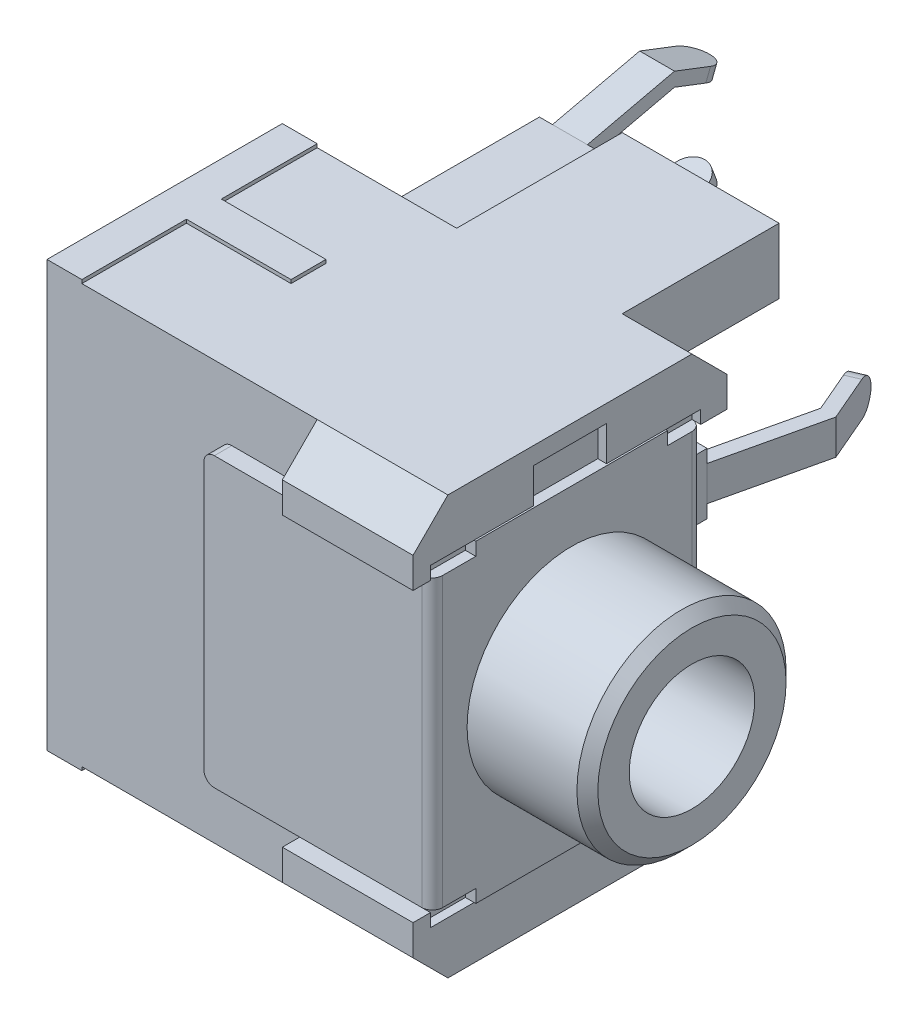
SolidWorks part; units mm, degrees
ref_plane "Front" through (0, 0, 0) normal (0, 0, 1) x (1, 0, 0)
ref_plane "Top" through (0, 0, 0) normal (0, 1, 0) x (1, 0, 0)
ref_plane "Right" through (0, 0, 0) normal (1, 0, 0) x (0, 0, -1)
sketch "Sketch1" plane through (0, 0, 0) normal (1, 0, 0) x (0, 0, -1)
  line L1 (-4.5, 6) -> (4.5, 6)
  line L2 (-4.5, 6) -> (-4.5, -6)
  line L3 (-4.5, -6) -> (4.5, -6)
  line L4 (4.5, 6) -> (4.5, -6)
  circle A0 centre (0, 0) radius 1.8
  dimension "ID" = 3.6
  dimension "H1" = 4.5
  dimension "Width" = 12
  dimension "Height" = 9
  dimension "H2" = 4.5
  dimension "W1" = 6
  dimension "W2" = 6
sketch "Sketch2" plane through (0, 0, 0) normal (0, 1, 0) x (1, 0, 0)
  line L0 (-3.5, 4.5) -> (-3.5, -4.5)
  line L1 (-3.5, 0) -> (0, 0) construction
  line L2 (-3.5, 3) -> (-3, 3) construction
  line L3 (-3.5, 3) -> (-3.5, -3) construction
  line L5 (-3.5, -3) -> (-3, -3) construction
  line L6 (-3, 3) -> (-3, -3) construction
  line L7 (-3, 3) -> (0, 3) construction
  line L8 (-3, 3) -> (-3, -3) construction
  line L9 (-3, -3) -> (0, -3) construction
  line L10 (-3.5, -4.5) -> (-15, -4.5)
  line L12 (-3.5, 4.5) -> (-15, 4.5)
  line L13 (-15, -4.5) -> (-15, 4.5)
  line L14 (0, 3) -> (0, -3) construction
  dimension "Length" = 11.5
  dimension "L2" = 3.5
  dimension "OD" = 6
  dimension "D_DIA" = 6
sketch "Sketch4" plane through (0, 0, 0) normal (0, 1, 0) x (1, 0, 0)
  line L1 (-3.5, 4.5) -> (-3.5, -4.5)
  line L4 (-15, -4.5) -> (-15, 4.5) construction
  line L5 (-3.5, -4.5) -> (-15, -4.5) construction
  line L15 (-3.5, 4.5) -> (-15, 4.5) construction
  line L20 (-15, -4.5) -> (-15, 4.5)
  line L21 (-3.5, -4.5) -> (-15, -4.5)
  line L31 (-3.5, 4.5) -> (-15, 4.5)
extrude "Extrude1" add sketch "Sketch4" along normal blind 6 and the other way blind 6
ref_plane "Plane1" through (-3, 0, 0) normal (1, 0, 0) x (0, 0, -1)
sketch "Sketch5" plane through (-3.5, 0, 0) normal (1, 0, 0) x (0, 0, -1)
  circle A0 centre (0, 0) radius 3
  dimension "OD" = 6
extrude "Extrude2" add sketch "Sketch5" along normal up to surface (0.5 mm away) up to plane "Plane1"
ref_plane "Plane2" through (-3, 0, 0) normal (1, 0, 0) x (0, 0, -1)
sketch "Sketch6" plane through (-3, 0, 0) normal (1, 0, 0) x (0, 0, -1)
  circle A0 centre (0, 0) radius 3
  dimension "D_DIA" = 6
extrude "Extrude3" add sketch "Sketch6" along normal up to surface (3 mm away) up to plane "Right"
sketch "Sketch12" plane through (0, 0, 0) normal (1, 0, 0) x (0, 0, -1)
  circle A0 centre (0, 0) radius 1.8 construction
  circle A3 centre (0, 0) radius 1.8
extrude "Cut-Extrude1" cut sketch "Sketch12" against normal up to surface (3.5 mm away) up to face at (-3.5, 0, 0)
chamfer "Chamfer1" distance 0.3 angle 45 1 edges at (0, 0, -3)
sketch "Sketch54" plane through (0, 0, 4.5) normal (0, 0, 1) x (1, 0, 0)
  line L0 (-15, -6) -> (-3.5, -6) construction
  line L1 (-15, 6) -> (-7.25, 6)
  line L2 (-15, 6) -> (-15, -6)
  line L3 (-15, -6) -> (-7.25, -6)
  line L4 (-7.25, 6) -> (-7.25, 4.125)
  line L5 (-3.5, 6) -> (-3.5, -6) construction
  line L6 (-7.25, 4.125) -> (-3.5, 4.125)
  line L8 (-7.25, -4.125) -> (-3.5, -4.125)
  line L9 (-3.5, 4.125) -> (-3.5, -4.125)
  line L10 (-7.25, -4.125) -> (-7.25, -6)
  point P12 (-3.5, 0)
  dimension "D1" = 8.25
  dimension "D3" = 3.75
extrude "Cut-Extrude17" cut sketch "Sketch54" against normal blind 1
sketch "Sketch56" plane through (0, 0, -4.5) normal (0, 0, -1) x (-1, 0, 0)
  line L8 (15, 6) -> (7.25, 6)
  line L9 (7.25, 6) -> (7.25, 4.125)
  line L10 (7.25, 4.125) -> (3.5, 4.125)
  line L11 (3.5, 4.125) -> (3.5, -4.125)
  line L12 (3.5, -4.125) -> (7.25, -4.125)
  line L13 (7.25, -4.125) -> (7.25, -6)
  line L14 (7.25, -6) -> (15, -6)
  line L15 (15, -6) -> (15, 6)
  line L16 (15, 6) -> (7.25, 6)
  line L17 (7.25, 6) -> (7.25, 4.125)
  line L18 (7.25, 4.125) -> (3.5, 4.125)
  line L19 (3.5, 4.125) -> (3.5, -4.125)
  line L20 (3.5, -4.125) -> (7.25, -4.125)
  line L21 (7.25, -4.125) -> (7.25, -6)
  line L22 (7.25, -6) -> (15, -6)
  line L23 (15, -6) -> (15, 6)
  dimension "D1" = 0
extrude "Cut-Extrude18" cut sketch "Sketch56" against normal blind 1.25
sketch "Sketch89" plane through (0, 0, -3.25) normal (0, 0, -1) x (-1, 0, 0)
  line L0 (3.5, 6) -> (3.5, 4.125) construction
  circle A0 centre (6.5, 5) radius 0.5
  circle A1 centre (6.5, -5) radius 0.5
  circle A2 centre (11.5, 0) radius 0.5
  dimension "D1" = 1
  dimension "D2" = 3
  dimension "D3" = 8
  dimension "D4" = 10
  dimension "D5" = 5
extrude "Extrude44" add sketch "Sketch89" along normal blind 3.75
sketch "Sketch58" plane through (0, 0, -3.25) normal (0, 0, -1) x (-1, 0, 0)
  line L0 (3.5, -4.125) -> (7.25, -4.125) construction
  line L1 (5.5, 6) -> (10, 6)
  line L2 (5.5, 6) -> (5.5, 4.125)
  line L3 (5.5, 4.125) -> (10, 4.125)
  line L4 (10, 6) -> (10, 4.125)
  line L5 (5.5, -6) -> (10, -6)
  line L6 (5.5, -6) -> (5.5, -4.125)
  line L7 (5.5, -4.125) -> (10, -4.125)
  line L8 (10, -6) -> (10, -4.125)
  line L10 (15, 6) -> (7.25, 6) construction
  line L11 (7.25, 4.125) -> (3.5, 4.125) construction
  line L12 (3.5, 6) -> (3.5, 4.125) construction
  dimension "D1" = 4.5
  dimension "D2" = 2
extrude "Extrude45" add sketch "Sketch58" along normal blind 4.75
sketch "Sketch63" plane through (0, 0, 0) normal (0, 1, 0) x (1, 0, 0)
  line L0 (-6.0646, 6.5) -> (-5.372, 9.5)
  line L1 (-5.372, 9.5) -> (-6.1325, 11.2684)
  line L2 (-15, 3.25) -> (-10, 3.25) construction
  line L3 (-6.1325, 11.2684) -> (-6.5, 11.1104)
  line L4 (-6.5, 11.1104) -> (-5.8074, 9.5)
  line L5 (-5.8074, 9.5) -> (-6.5, 6.5)
  line L9 (-3.5, -4.5) -> (-3.5, 4.5) construction
  line L10 (-10, 8) -> (-5.5, 8) construction
  line L14 (-6.5, 6.5) -> (-6.5, 3.25)
  line L15 (-6.5, 3.25) -> (-6.0646, 3.25)
  line L16 (-6.0646, 6.5) -> (-6.0646, 3.25)
  dimension "D1" = 0.4
  dimension "D2" = 103
  dimension "D3" = 1.5
  dimension "D5" = 3
  dimension "D6" = 6.5
extrude "Extrude46" add sketch "Sketch63" along normal mid plane 1
fillet "Fillet34" 2 edges at (-6.3163, 0.5, -11.1894) (-6.3163, -0.5, -11.1894) type full round first side face at (-6.1176, 0.5, -7.6098) second side face at (-6.1176, -0.5, -7.6098) middle face at (-6.3163, 0, -11.1894)
sketch "Sketch127" plane through (0, 0, -3.25) normal (0, 0, -1) x (-1, 0, 0)
  line L0 (3.45, 4.125) -> (3.45, -4.125)
  line L1 (3.45, -4.125) -> (10, -4.125)
  line L2 (10, -4.125) -> (10, -1)
  line L3 (10, -1) -> (6.5, -1)
  line L4 (6.5, -1) -> (6.5, 1)
  line L5 (6.5, 1) -> (10, 1)
  line L6 (10, 1) -> (10, 4.125)
  line L7 (10, 4.125) -> (3.45, 4.125)
  line L8 (5.5, 4.125) -> (10, 4.125) construction
  line L9 (10, -4.125) -> (5.5, -4.125) construction
  line L10 (3.5, 6) -> (3.5, 4.125) construction
  line L11 (6.5, 0.5) -> (6.5, -0.5) construction
  line L12 (3.5, 4.125) -> (3.5, -4.125) construction
  line L13 (0, 0) -> (4.7323, 0) construction
  line L14 (7.5, 3.0625) -> (9, 3.0625)
  line L15 (7.5, 3.0625) -> (7.5, 2.0625)
  line L16 (7.5, 2.0625) -> (9, 2.0625)
  line L17 (9, 3.0625) -> (9, 2.0625)
  line L18 (7.5, -2.0625) -> (9, -2.0625)
  line L19 (7.5, -2.0625) -> (7.5, -3.0625)
  line L20 (7.5, -3.0625) -> (9, -3.0625)
  line L21 (9, -2.0625) -> (9, -3.0625)
  line L22 (9, 2.5625) -> (10, 2.5625) construction
  dimension "D1" = 2
  dimension "D2" = 0.05
  dimension "D3" = 4
  dimension "D4" = 1.5
  dimension "D5" = 1
extrude "Extrude67" add sketch "Sketch127" along normal blind 0.5 and the other way blind 0.5 separate body
fillet "Fillet53" radius 0.3 15 edges at (-10, 1, -3.25) (-6.5, 1, -3.25) (-6.5, -1, -3.25) (-10, -1, -3.25) (-3.45, 0, -3.75) (-10, 4.125, -3.25) (-10, -4.125, -3.25) (-7.5, -3.0625, -3.25) (-7.5, -2.0625, -3.25) (-9, -3.0625, -3.25) (-9, -2.0625, -3.25) (-7.5, 2.0625, -3.25) (-9, 2.0625, -3.25) (-9, 3.0625, -3.25) (-7.5, 3.0625, -3.25)
sketch "Sketch141" plane through (0, 0, -3.25) normal (0, 0, -1) x (-1, 0, 0)
  line L0 (0, 0) -> (2.0768, 0) construction
  line L1 (7.5, -2.3625) -> (7.5, -2.7625) construction
  line L2 (7.8, -3.0625) -> (8.7, -3.0625) construction
  line L3 (9, -2.7625) -> (9, -2.3625) construction
  line L4 (8.7, -2.0625) -> (7.8, -2.0625) construction
  line L5 (9, 2.3625) -> (9, 2.7625) construction
  line L6 (7.8, 2.0625) -> (8.7, 2.0625) construction
  line L7 (7.5, 2.7625) -> (7.5, 2.3625) construction
  line L8 (8.7, 3.0625) -> (7.8, 3.0625) construction
  line L9 (7.5, -2.3625) -> (7.5, -2.7625)
  line L11 (7.8, -3.0625) -> (8.7, -3.0625)
  line L12 (9, -2.7625) -> (9, -2.3625)
  line L13 (8.7, -2.0625) -> (7.8, -2.0625)
  line L14 (9, 2.3625) -> (9, 2.7625)
  line L15 (7.8, 2.0625) -> (8.7, 2.0625)
  line L16 (7.5, 2.7625) -> (7.5, 2.3625)
  line L17 (8.7, 3.0625) -> (7.8, 3.0625)
  arc A2 (7.8, -2.0625) -> (7.5, -2.3625) centre (7.8, -2.3625) ccw construction
  arc A3 (7.5, -2.7625) -> (7.8, -3.0625) centre (7.8, -2.7625) ccw construction
  arc A4 (8.7, -3.0625) -> (9, -2.7625) centre (8.7, -2.7625) ccw construction
  arc A5 (9, -2.3625) -> (8.7, -2.0625) centre (8.7, -2.3625) ccw construction
  arc A6 (8.7, 2.0625) -> (9, 2.3625) centre (8.7, 2.3625) ccw construction
  arc A7 (7.5, 2.3625) -> (7.8, 2.0625) centre (7.8, 2.3625) ccw construction
  arc A8 (7.8, 3.0625) -> (7.5, 2.7625) centre (7.8, 2.7625) ccw construction
  arc A9 (9, 2.7625) -> (8.7, 3.0625) centre (8.7, 2.7625) ccw construction
  arc A10 (7.8, -2.0625) -> (7.5, -2.3625) centre (7.8, -2.3625) ccw
  arc A11 (7.5, -2.7625) -> (7.8, -3.0625) centre (7.8, -2.7625) ccw
  arc A12 (8.7, -3.0625) -> (9, -2.7625) centre (8.7, -2.7625) ccw
  arc A13 (9, -2.3625) -> (8.7, -2.0625) centre (8.7, -2.3625) ccw
  arc A14 (8.7, 2.0625) -> (9, 2.3625) centre (8.7, 2.3625) ccw
  arc A15 (7.5, 2.3625) -> (7.8, 2.0625) centre (7.8, 2.3625) ccw
  arc A16 (7.8, 3.0625) -> (7.5, 2.7625) centre (7.8, 2.7625) ccw
  arc A17 (9, 2.7625) -> (8.7, 3.0625) centre (8.7, 2.7625) ccw
extrude "Extrude73" add sketch "Sketch141" along normal blind 0.5 separate body
sketch "Sketch128" plane through (0, 0, 3.5) normal (0, 0, 1) x (1, 0, 0)
  line L1 (-10, 4.125) -> (-3.45, 4.125)
  line L2 (-10, 4.125) -> (-10, -4.125)
  line L3 (-10, -4.125) -> (-3.45, -4.125)
  line L4 (-3.45, 4.125) -> (-3.45, -4.125)
  line L5 (-10, 1.3) -> (-10, 3.825) construction
  line L6 (-9.7, 4.125) -> (-3.45, 4.125) construction
  line L7 (-3.5, -4.125) -> (-10, -4.125) construction
  line L8 (-3.5, 6) -> (-3.5, 4.125) construction
  line L9 (0, 0) -> (-4.1973, 0) construction
  dimension "D1" = 0.05
extrude "Extrude68" add sketch "Sketch128" along normal blind 0.5 and the other way up to surface (6.25 mm away) separate body other way up to face at (-8.25, -2.5625, -2.75)
fillet "Fillet52" radius 0.3 3 edges at (-10, -4.125, 0.625) (-10, 4.125, 0.625) (-3.45, 0, 4)
sketch "Sketch90" plane through (0, 0.5, 0) normal (0, 1, 0) x (-1, 0, 0)
  line L1 (6.0646, -6.5) -> (6.5, -6.5)
  line L2 (6.0646, -6.5) -> (6.0646, -3.25)
  line L3 (6.0646, -3.25) -> (6.5, -3.25)
  line L4 (6.5, -6.5) -> (6.5, -3.25)
extrude "Extrude49" add sketch "Sketch90" along normal blind 0.375 and the other way blind 1.375
ref_plane "Plane6" through (-11.5, 0, 0) normal (1, 0, 0) x (0, 0, -1)
sketch "Sketch64" plane through (-11.5, 0, 0) normal (1, 0, 0) x (0, 0, -1)
  line L0 (3.25, 5.2) -> (8, 5.2)
  line L1 (8, 5.2) -> (10.5, 5.7772)
  line L2 (10.5, 5.7772) -> (12, 5.2)
  line L3 (12, 5.2) -> (11.8659, 4.8516)
  line L4 (11.8659, 4.8516) -> (10.5, 5.3772)
  line L5 (10.5, 5.3772) -> (8, 4.8)
  line L6 (8, 4.8) -> (3.25, 4.8)
  line L7 (3.25, 4.8) -> (3.25, 5.2)
  line L8 (8, 6) -> (8, 4.125) construction
  line L9 (3.25, 4.125) -> (3.25, -4.125) construction
  point P8 (3.25, 5)
  dimension "D1" = 0.4
  dimension "D2" = 5
  dimension "D3" = 4
  dimension "D4" = 2.5
  dimension "D5" = 103
extrude "Extrude47" add sketch "Sketch64" along normal mid plane 1
fillet "Fillet35" 2 edges at (-11, 5.0258, -11.933) (-12, 5.0258, -11.933) type full round first side face at (-11, 5.1507, -8.4207) second side face at (-12, 5.1507, -8.4207) middle face at (-11.5, 5.0258, -11.933)
sketch "Sketch91" plane through (-12, 0, 0) normal (-1, 0, 0) x (0, 0, 1)
  line L1 (-3.25, 4.8) -> (-8, 4.8)
  line L2 (-3.25, 4.8) -> (-3.25, 5.2)
  line L3 (-3.25, 5.2) -> (-8, 5.2)
  line L4 (-8, 4.8) -> (-8, 5.2)
extrude "Extrude50" add sketch "Sketch91" along normal blind 0.375 and the other way blind 1.375
mirror "Mirror4" about plane through (0, 0, 0) normal (0, 1, 0) of "Extrude50", "Extrude47", "Fillet35"
ref_plane "Plane7" through (0, 3.75, 0) normal (0, 1, 0) x (-1, 0, 0)
mirror "Mirror5" about plane through (0, 3.75, 0) normal (0, 1, 0) of "Extrude50", "Extrude47", "Fillet35"
sketch "Sketch65" plane through (0, 0, -3.25) normal (0, 0, -1) x (-1, 0, 0)
  line L1 (11, -2.3) -> (12, -2.3)
  line L2 (11, -2.3) -> (11, -2.7)
  line L3 (11, -2.7) -> (12, -2.7)
  line L4 (12, -2.3) -> (12, -2.7)
  point P4 (12, -2.5)
  dimension "D1" = 1
  dimension "D2" = 0.4
  dimension "D3" = 2.5
extrude "Extrude48" add sketch "Sketch65" along normal blind 7.25
fillet "Fillet36" 2 edges at (-11, -2.5, -10.5) (-12, -2.5, -10.5) type full round first side face at (-11, -2.5, -6.875) second side face at (-12, -2.5, -6.875) middle face at (-11.5, -2.5, -10.5)
sketch "Sketch93" plane through (-12, 0, 0) normal (-1, 0, 0) x (0, 0, 1)
  line L0 (-3.25, -6) -> (-3.25, 6) construction
  line L1 (-6.5, -2.3) -> (-3.25, -2.3)
  line L2 (-6.5, -2.3) -> (-6.5, -2.7)
  line L3 (-6.5, -2.7) -> (-3.25, -2.7)
  line L4 (-3.25, -2.3) -> (-3.25, -2.7)
  line L5 (-10, -2.3) -> (-3.25, -2.3) construction
  line L6 (-10, -2.7) -> (-3.25, -2.7) construction
  dimension "D1" = 3.25
extrude "Extrude51" add sketch "Sketch93" along normal blind 0.375 and the other way blind 1.375
sketch "Sketch142" plane through (0, 6, 0) normal (0, 1, 0) x (-1, 0, 0)
  line L0 (-1.5698, 0) -> (16.7437, 0) construction
  line L1 (15, -3.25) -> (14, -3.25)
  line L2 (15, -3.25) -> (10, -3.25) construction
  line L3 (14, -3.25) -> (14, -0.5)
  line L4 (14, -0.5) -> (11, -0.5)
  line L5 (11, -0.5) -> (11, 0.5)
  line L6 (11, 0.5) -> (14, 0.5)
  line L7 (14, 0.5) -> (14, 3.5)
  line L8 (7.25, 3.5) -> (15, 3.5) construction
  line L9 (14, 3.5) -> (15, 3.5)
  line L10 (15, -3.25) -> (15, 3.5) construction
  line L11 (15, 3.5) -> (15, -3.25)
  dimension "D1" = 1
  dimension "D2" = 1
  dimension "D3" = 4
extrude "T-EXTRUSION" add sketch "Sketch142" along normal blind 0.1
mirror "T-MIRRORED" about plane through (0, 0, 0) normal (0, 1, 0) of "T-EXTRUSION"
sketch "Sketch143" plane through (-3.5, 0, 0) normal (1, 0, 0) x (0, 0, -1)
  line L0 (-5.3873, 0) -> (11.4883, 0) construction
  line L1 (-3.5, 4.125) -> (-4.5, 4.125) construction
  line L2 (-4, 4.125) -> (3.75, 4.125)
  line L3 (-4, 4.125) -> (-4, 4.5)
  line L4 (-4, 4.5) -> (3.75, 4.5)
  line L5 (3.75, 4.125) -> (3.75, 4.5)
  line L6 (3.75, 4.125) -> (3.75, -4.125) construction
  line L7 (3.75, -4.125) -> (3.75, -4.5)
  line L8 (-4, -4.5) -> (3.75, -4.5)
  line L9 (-4, -4.125) -> (-4, -4.5)
  line L10 (-4, -4.125) -> (3.75, -4.125)
  dimension "D1" = 9
extrude "FRONT_CUT" cut sketch "Sketch143" against normal blind 0.25
sketch "Sketch144" plane through (-3.45, 0, 0) normal (1, 0, 0) x (0, 0, -1)
  line L0 (-4.9785, 0) -> (11.4236, 0) construction
  line L1 (-3.5, 4.125) -> (3.25, 4.125) construction
  line L2 (-2.75, 4.125) -> (2.75, 4.125)
  line L3 (-2.75, 4.125) -> (-2.75, 4.5)
  line L4 (-2.75, 4.5) -> (2.75, 4.5)
  line L5 (2.75, 4.125) -> (2.75, 4.5)
  line L6 (3.75, 4.5) -> (-4, 4.5) construction
  line L7 (0, 0) -> (0, 7.903) construction
  line L8 (2.75, -4.125) -> (2.75, -4.5)
  line L9 (-2.75, -4.5) -> (2.75, -4.5)
  line L10 (-2.75, -4.125) -> (-2.75, -4.5)
  line L11 (-2.75, -4.125) -> (2.75, -4.125)
  dimension "D1" = 5.5
extrude "WIDEN_METAL" add sketch "Sketch144" against normal up to body separate body
sketch "Sketch145" plane through (-3.5, 0, 0) normal (1, 0, 0) x (0, 0, -1)
  line L0 (0, 0) -> (0, 10.5822) construction
  line L1 (-1.05, 4.5) -> (1.05, 4.5)
  line L2 (-1.05, 4.5) -> (-1.05, 5.5)
  line L3 (-1.05, 5.5) -> (1.05, 5.5)
  line L4 (1.05, 4.5) -> (1.05, 5.5)
  line L5 (2.75, 4.5) -> (-2.75, 4.5) construction
  dimension "D1" = 1
  dimension "D2" = 2.1
extrude "Cut-Extrude19" cut sketch "Sketch145" against normal up to surface (0.25 mm away) up to face at (-3.75, 4.3125, 3.375)
chamfer "FRONT_CHAMFER" distance 1 angle 45 4 edges at (-4.5, 6, -4.5) (-5.375, 6, 4.5) (-4.5, -6, -4.5) (-5.375, -6, 4.5)
equation "\"D2@Extrude1\" = \"W2@Sketch1\""
